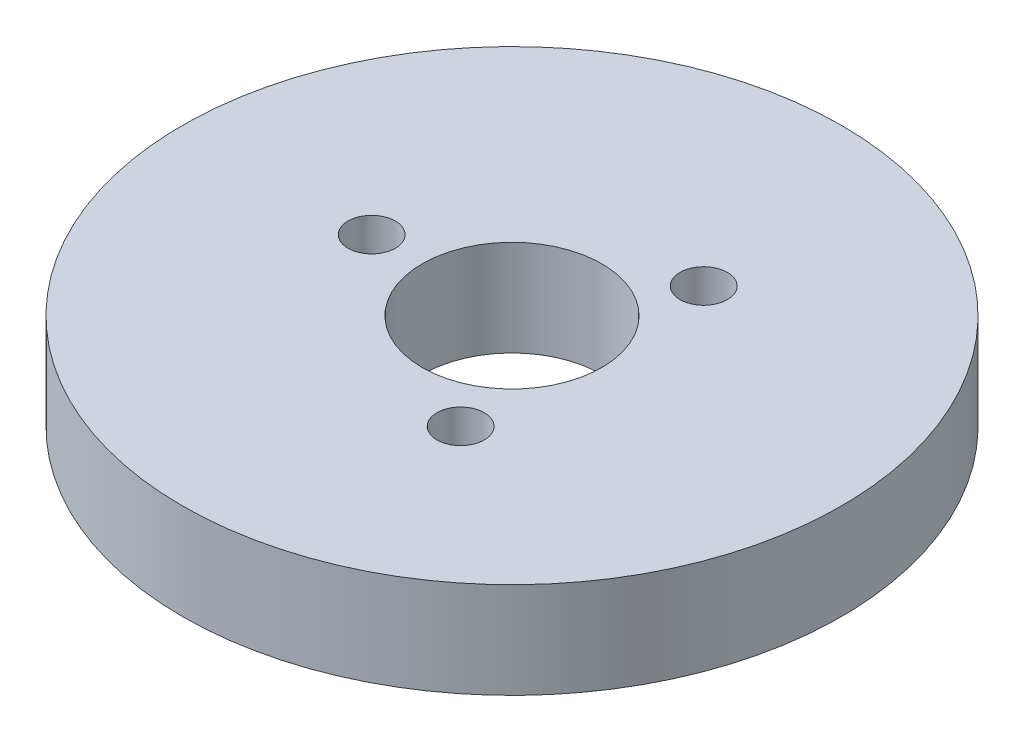
SolidWorks part; units mm, degrees
ref_plane "Front Plane" through (0, 0, 0) normal (0, 0, 1) x (1, 0, 0)
ref_plane "Top Plane" through (0, 0, 0) normal (0, 1, 0) x (1, 0, 0)
ref_plane "Right Plane" through (0, 0, 0) normal (1, 0, 0) x (0, 0, -1)
sketch "Sketch1" plane through (0, 0, 0) normal (0, 1, 0) x (1, 0, 0)
  circle A0 centre (0, 0) radius 27.5
  dimension "FLANGE_OD" = 55
extrude "Boss-Extrude1" add sketch "Sketch1" along normal blind 8
sketch "Sketch2" plane through (0, 0, 0) normal (0, 1, 0) x (1, 0, 0)
  circle A0 centre (0, 0) radius 7.5
  dimension "BORE_D" = 15
extrude "Cut-Extrude1" cut sketch "Sketch2" along normal through all
sketch "Sketch3" plane through (0, 8, 0) normal (0, 1, 0) x (1, 0, 0)
  circle A0 centre (0, 0) radius 11.7098 construction
  circle A1 centre (-11.7098, 0) radius 1.9733
  dimension "BOLT_D" = 3.9466
  dimension "BOLT_PCD" = 23.4197
extrude "Cut-Extrude2" cut sketch "Sketch3" against normal blind 6.6429
pattern_circular "CirPattern1" count 3 over 360 about axis through (0, 0, 0) along (0, 1, 0) of "Cut-Extrude2"
